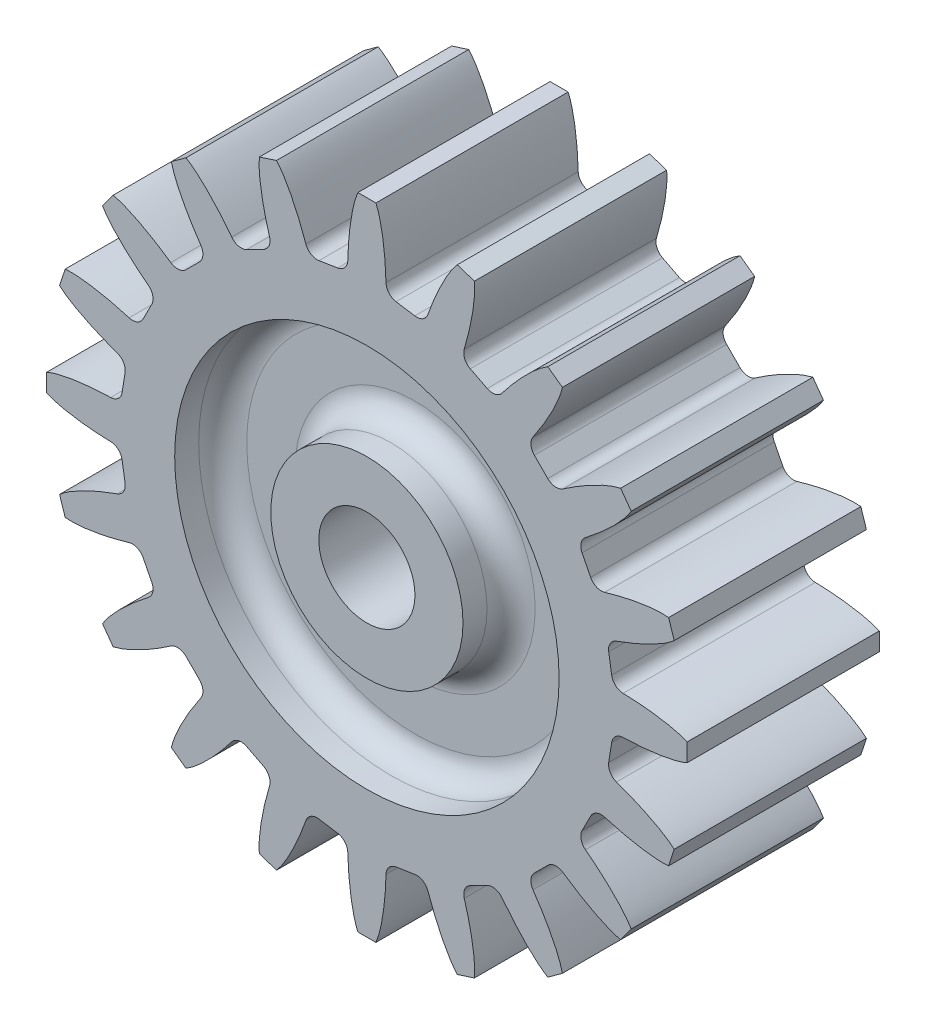
SolidWorks part; units mm, degrees
ref_plane "Front Plane" through (0, 0, 0) normal (0, 0, 1) x (1, 0, 0)
ref_plane "Top Plane" through (0, 0, 0) normal (0, 1, 0) x (1, 0, 0)
ref_plane "Right Plane" through (0, 0, 0) normal (1, 0, 0) x (0, 0, -1)
sketch "Sketch1" plane through (0, 0, 0) normal (0, 0, 1) x (1, 0, 0)
  line L0 (0, -63.5) -> (0, 63.5) construction
  line L1 (63.5, 0) -> (-63.5, 0) construction
  line L2 (-1.1938, 42.3123) -> (1.1938, 42.3123)
  line L3 (-14.2106, 39.8724) -> (-11.9398, 40.6103)
  line L4 (11.9398, 40.6103) -> (14.2106, 39.8724)
  line L5 (-3.8534, 32.3448) -> (-6.3303, 31.9525)
  line L6 (3.8534, 32.3448) -> (6.3303, 31.9525)
  line L7 (23.9047, 34.933) -> (25.8363, 33.5296)
  line L8 (33.5296, 25.8363) -> (34.933, 23.9047)
  line L9 (39.8724, 14.2106) -> (40.6103, 11.9398)
  line L10 (42.3123, 1.1938) -> (42.3123, -1.1938)
  line L11 (40.6103, -11.9398) -> (39.8724, -14.2106)
  line L12 (34.933, -23.9047) -> (33.5296, -25.8363)
  line L13 (13.6599, 29.571) -> (15.8943, 28.4325)
  line L14 (22.1293, 23.9025) -> (23.9025, 22.1293)
  line L15 (25.8363, -33.5296) -> (23.9047, -34.933)
  line L16 (14.2106, -39.8724) -> (11.9398, -40.6103)
  line L17 (1.1938, -42.3123) -> (-1.1938, -42.3123)
  line L18 (-14.2106, -39.8724) -> (-11.9398, -40.6103)
  line L19 (-25.8363, -33.5296) -> (-23.9047, -34.933)
  line L20 (-34.933, -23.9047) -> (-33.5296, -25.8363)
  line L21 (-39.8724, -14.2106) -> (-40.6103, -11.9398)
  line L22 (-42.3123, 1.1938) -> (-42.3123, -1.1938)
  line L23 (-39.8724, 14.2106) -> (-40.6103, 11.9398)
  line L24 (-34.933, 23.9047) -> (-33.5296, 25.8363)
  line L25 (-25.8363, 33.5296) -> (-23.9047, 34.933)
  line L26 (-15.8943, 28.4325) -> (-13.6599, 29.571)
  line L27 (-22.1293, 23.9025) -> (-23.9025, 22.1293)
  line L28 (-29.571, 13.6599) -> (-28.4325, 15.8943)
  line L29 (-31.9525, 6.3303) -> (-32.3448, 3.8534)
  line L30 (-32.3448, -3.8534) -> (-31.9525, -6.3303)
  line L31 (-29.571, -13.6599) -> (-28.4325, -15.8943)
  line L32 (-23.9025, -22.1293) -> (-22.1293, -23.9025)
  line L33 (-15.8943, -28.4325) -> (-13.6599, -29.571)
  line L34 (-6.3303, -31.9525) -> (-3.8534, -32.3448)
  line L35 (3.8534, -32.3448) -> (6.3303, -31.9525)
  line L36 (13.6599, -29.571) -> (15.8943, -28.4325)
  line L37 (22.1293, -23.9025) -> (23.9025, -22.1293)
  line L38 (29.571, -13.6599) -> (28.4325, -15.8943)
  line L39 (32.3448, -3.8534) -> (31.9525, -6.3303)
  line L40 (31.9525, 6.3303) -> (32.3448, 3.8534)
  line L41 (28.4325, 15.8943) -> (29.571, 13.6599)
  circle A0 centre (0, 0) radius 6.35
  circle A1 centre (0, 0) radius 12.7
  circle A2 centre (0, 0) radius 25.4
  circle A3 centre (0, 0) radius 42.3291 construction
  circle A4 centre (0, 0) radius 32.6517 construction
  circle A5 centre (0, 0) radius 38.0873 construction
  arc A6 (-3.8534, 32.3448) -> (-2.5255, 33.8596) centre (-4.0998, 33.9002) ccw
  arc A7 (-8.0613, 32.9828) -> (-6.3303, 31.9525) centre (-6.5766, 33.5079) ccw
  arc A8 (8.0613, 32.9828) -> (6.3303, 31.9525) centre (6.5766, 33.5079) cw
  arc A9 (2.5255, 33.8596) -> (3.8534, 32.3448) centre (4.0998, 33.9002) ccw
  arc A10 (12.8651, 31.422) -> (13.6599, 29.571) centre (14.3749, 30.9741) ccw
  arc A11 (17.859, 28.8775) -> (15.8943, 28.4325) centre (16.6092, 29.8356) cw
  arc A12 (25.9085, 21.9454) -> (23.9025, 22.1293) centre (25.0161, 23.2428) cw
  arc A13 (21.9454, 25.9085) -> (22.1293, 23.9025) centre (23.2428, 25.0161) ccw
  arc A14 (-13.6599, 29.571) -> (-12.8651, 31.422) centre (-14.3749, 30.9741) ccw
  arc A15 (-17.859, 28.8775) -> (-15.8943, 28.4325) centre (-16.6092, 29.8356) ccw
  arc A16 (-33.8596, 2.5255) -> (-32.3448, 3.8534) centre (-33.9002, 4.0998) ccw
  arc A17 (-31.9525, 6.3303) -> (-32.9828, 8.0613) centre (-33.5079, 6.5766) ccw
  arc A18 (-31.422, 12.8651) -> (-29.571, 13.6599) centre (-30.9741, 14.3749) ccw
  arc A19 (-28.4325, 15.8943) -> (-28.8775, 17.859) centre (-29.8356, 16.6092) ccw
  arc A20 (-25.9085, 21.9454) -> (-23.9025, 22.1293) centre (-25.0161, 23.2428) ccw
  arc A21 (-22.1293, 23.9025) -> (-21.9454, 25.9085) centre (-23.2428, 25.0161) ccw
  arc A22 (-32.9828, -8.0613) -> (-31.9525, -6.3303) centre (-33.5079, -6.5766) ccw
  arc A23 (-32.3448, -3.8534) -> (-33.8596, -2.5255) centre (-33.9002, -4.0998) ccw
  arc A24 (-28.8775, -17.859) -> (-28.4325, -15.8943) centre (-29.8356, -16.6092) ccw
  arc A25 (-31.422, -12.8651) -> (-29.571, -13.6599) centre (-30.9741, -14.3749) cw
  arc A26 (-21.9454, -25.9085) -> (-22.1293, -23.9025) centre (-23.2428, -25.0161) ccw
  arc A27 (-23.9025, -22.1293) -> (-25.9085, -21.9454) centre (-25.0161, -23.2428) ccw
  arc A28 (-12.8651, -31.422) -> (-13.6599, -29.571) centre (-14.3749, -30.9741) ccw
  arc A29 (-15.8943, -28.4325) -> (-17.859, -28.8775) centre (-16.6092, -29.8356) ccw
  arc A30 (-2.5255, -33.8596) -> (-3.8534, -32.3448) centre (-4.0998, -33.9002) ccw
  arc A31 (-6.3303, -31.9525) -> (-8.0613, -32.9828) centre (-6.5766, -33.5079) ccw
  arc A32 (8.0613, -32.9828) -> (6.3303, -31.9525) centre (6.5766, -33.5079) ccw
  arc A33 (2.5255, -33.8596) -> (3.8534, -32.3448) centre (4.0998, -33.9002) cw
  arc A34 (17.859, -28.8775) -> (15.8943, -28.4325) centre (16.6092, -29.8356) ccw
  arc A35 (13.6599, -29.571) -> (12.8651, -31.422) centre (14.3749, -30.9741) ccw
  arc A36 (21.9454, -25.9085) -> (22.1293, -23.9025) centre (23.2428, -25.0161) cw
  arc A37 (25.9085, -21.9454) -> (23.9025, -22.1293) centre (25.0161, -23.2428) ccw
  arc A38 (28.4325, -15.8943) -> (28.8775, -17.859) centre (29.8356, -16.6092) ccw
  arc A39 (31.422, -12.8651) -> (29.571, -13.6599) centre (30.9741, -14.3749) ccw
  arc A40 (32.9828, -8.0613) -> (31.9525, -6.3303) centre (33.5079, -6.5766) cw
  arc A41 (33.8596, -2.5255) -> (32.3448, -3.8534) centre (33.9002, -4.0998) ccw
  arc A42 (32.3448, 3.8534) -> (33.8596, 2.5255) centre (33.9002, 4.0998) ccw
  arc A43 (32.9828, 8.0613) -> (31.9525, 6.3303) centre (33.5079, 6.5766) ccw
  arc A44 (29.571, 13.6599) -> (31.422, 12.8651) centre (30.9741, 14.3749) ccw
  arc A45 (28.8775, 17.859) -> (28.4325, 15.8943) centre (29.8356, 16.6092) ccw
  ellipse E0 centre (0, 32.6517) end of major axis (0, 43.5952) minor radius 2.541 (2.5255, 33.8596) -> (1.1938, 42.3123) ccw
  ellipse E1 centre (19.1922, 26.4158) end of major axis (12.7598, 17.5623) minor radius 2.541 (21.9454, 25.9085) -> (25.8363, 33.5296) ccw
  ellipse E2 centre (26.4158, 19.1922) end of major axis (35.2692, 25.6246) minor radius 2.541 (28.8775, 17.859) -> (34.933, 23.9047) ccw
  ellipse E3 centre (31.0536, -10.0899) end of major axis (20.6457, -6.7082) minor radius 2.541 (31.422, -12.8651) -> (39.8724, -14.2106) ccw
  ellipse E4 centre (31.0536, 10.0899) end of major axis (20.6457, 6.7082) minor radius 2.541 (32.9828, 8.0613) -> (40.6103, 11.9398) ccw
  ellipse E5 centre (32.6517, 0) end of major axis (43.5952, 0) minor radius 2.541 (33.8596, -2.5255) -> (42.3123, -1.1938) ccw
  ellipse E6 centre (0, 32.6517) end of major axis (0, 43.5952) minor radius 2.541 (-1.1938, 42.3123) -> (-2.5255, 33.8596) ccw
  ellipse E7 centre (26.4158, -19.1922) end of major axis (35.2692, -25.6246) minor radius 2.541 (25.9085, -21.9454) -> (33.5296, -25.8363) ccw
  ellipse E8 centre (-10.0899, 31.0536) end of major axis (-6.7082, 20.6457) minor radius 2.541 (-14.2106, 39.8724) -> (-12.8651, 31.422) ccw
  ellipse E9 centre (10.0899, -31.0536) end of major axis (13.4717, -41.4615) minor radius 2.541 (8.0613, -32.9828) -> (11.9398, -40.6103) ccw
  ellipse E10 centre (10.0899, 31.0536) end of major axis (6.7082, 20.6457) minor radius 2.541 (11.9398, 40.6103) -> (8.0613, 32.9828) ccw
  ellipse E11 centre (-10.0899, -31.0536) end of major axis (-13.4717, -41.4615) minor radius 2.541 (-12.8651, -31.422) -> (-14.2106, -39.8724) ccw
  ellipse E12 centre (-19.1922, -26.4158) end of major axis (-25.6246, -35.2692) minor radius 2.541 (-21.9454, -25.9085) -> (-25.8363, -33.5296) ccw
  ellipse E13 centre (-26.4158, -19.1922) end of major axis (-17.5623, -12.7598) minor radius 2.541 (-28.8775, -17.859) -> (-34.933, -23.9047) ccw
  ellipse E14 centre (19.1922, -26.4158) end of major axis (12.7598, -17.5623) minor radius 2.541 (17.859, -28.8775) -> (23.9047, -34.933) ccw
  ellipse E15 centre (-32.6517, 0) end of major axis (-43.5952, 0) minor radius 2.541 (-33.8596, 2.5255) -> (-42.3123, 1.1938) ccw
  ellipse E16 centre (-31.0536, 10.0899) end of major axis (-41.4615, 13.4717) minor radius 2.541 (-31.422, 12.8651) -> (-39.8724, 14.2106) ccw
  ellipse E17 centre (-26.4158, 19.1922) end of major axis (-17.5623, 12.7598) minor radius 2.541 (-25.9085, 21.9454) -> (-33.5296, 25.8363) ccw
  ellipse E18 centre (-19.1922, 26.4158) end of major axis (-25.6246, 35.2692) minor radius 2.541 (-17.859, 28.8775) -> (-23.9047, 34.933) ccw
  ellipse E19 centre (-10.0899, 31.0536) end of major axis (-6.7082, 20.6457) minor radius 2.541 (-8.0613, 32.9828) -> (-11.9398, 40.6103) ccw
  ellipse E20 centre (10.0899, 31.0536) end of major axis (6.7082, 20.6457) minor radius 2.541 (12.8651, 31.422) -> (14.2106, 39.8724) ccw
  ellipse E21 centre (26.4158, -19.1922) end of major axis (35.2692, -25.6246) minor radius 2.541 (34.933, -23.9047) -> (28.8775, -17.859) ccw
  ellipse E22 centre (-31.0536, -10.0899) end of major axis (-20.6457, -6.7082) minor radius 2.541 (-32.9828, -8.0613) -> (-40.6103, -11.9398) ccw
  ellipse E23 centre (31.0536, -10.0899) end of major axis (20.6457, -6.7082) minor radius 2.541 (40.6103, -11.9398) -> (32.9828, -8.0613) ccw
  ellipse E24 centre (32.6517, 0) end of major axis (43.5952, 0) minor radius 2.541 (42.3123, 1.1938) -> (33.8596, 2.5255) ccw
  ellipse E25 centre (31.0536, 10.0899) end of major axis (20.6457, 6.7082) minor radius 2.541 (39.8724, 14.2106) -> (31.422, 12.8651) ccw
  ellipse E26 centre (0, -32.6517) end of major axis (0, -43.5952) minor radius 2.541 (-2.5255, -33.8596) -> (-1.1938, -42.3123) ccw
  ellipse E27 centre (26.4158, 19.1922) end of major axis (35.2692, 25.6246) minor radius 2.541 (33.5296, 25.8363) -> (25.9085, 21.9454) ccw
  ellipse E28 centre (19.1922, 26.4158) end of major axis (12.7598, 17.5623) minor radius 2.541 (23.9047, 34.933) -> (17.859, 28.8775) ccw
  ellipse E29 centre (-19.1922, 26.4158) end of major axis (-25.6246, 35.2692) minor radius 2.541 (-25.8363, 33.5296) -> (-21.9454, 25.9085) ccw
  ellipse E30 centre (-26.4158, 19.1922) end of major axis (-17.5623, 12.7598) minor radius 2.541 (-34.933, 23.9047) -> (-28.8775, 17.859) ccw
  ellipse E31 centre (-31.0536, 10.0899) end of major axis (-41.4615, 13.4717) minor radius 2.541 (-40.6103, 11.9398) -> (-32.9828, 8.0613) ccw
  ellipse E32 centre (-32.6517, 0) end of major axis (-43.5952, 0) minor radius 2.541 (-42.3123, -1.1938) -> (-33.8596, -2.5255) ccw
  ellipse E33 centre (-31.0536, -10.0899) end of major axis (-20.6457, -6.7082) minor radius 2.541 (-39.8724, -14.2106) -> (-31.422, -12.8651) ccw
  ellipse E34 centre (-26.4158, -19.1922) end of major axis (-17.5623, -12.7598) minor radius 2.541 (-33.5296, -25.8363) -> (-25.9085, -21.9454) ccw
  ellipse E35 centre (19.1922, -26.4158) end of major axis (12.7598, -17.5623) minor radius 2.541 (25.8363, -33.5296) -> (21.9454, -25.9085) ccw
  ellipse E36 centre (10.0899, -31.0536) end of major axis (13.4717, -41.4615) minor radius 2.541 (14.2106, -39.8724) -> (12.8651, -31.422) ccw
  ellipse E37 centre (0, -32.6517) end of major axis (0, -43.5952) minor radius 2.541 (1.1938, -42.3123) -> (2.5255, -33.8596) ccw
  ellipse E38 centre (-10.0899, -31.0536) end of major axis (-13.4717, -41.4615) minor radius 2.541 (-11.9398, -40.6103) -> (-8.0613, -32.9828) ccw
  ellipse E39 centre (-19.1922, -26.4158) end of major axis (-25.6246, -35.2692) minor radius 2.541 (-23.9047, -34.933) -> (-17.859, -28.8775) ccw
  point P11 (0, 0)
  point P13 (0, 0)
  point P15 (-1.1938, 42.3123)
  point P21 (1.1938, 42.3123)
  point P22 (2.2139, 38.0229)
  point P23 (-2.2139, 38.0229)
  point P28 (11.9398, 40.6103)
  point P34 (14.2106, 39.8724)
  point P35 (13.8553, 35.4778)
  point P36 (9.6442, 36.8461)
  point P38 (23.9047, 34.933)
  point P44 (25.8363, 33.5296)
  point P45 (24.1404, 29.4599)
  point P46 (20.5582, 32.0625)
  point P48 (33.5296, 25.8363)
  point P54 (34.933, 23.9047)
  point P55 (32.0625, 20.5582)
  point P56 (29.4599, 24.1404)
  point P58 (39.8724, 14.2106)
  point P64 (40.6103, 11.9398)
  point P65 (36.8461, 9.6442)
  point P66 (35.4778, 13.8553)
  point P68 (42.3123, 1.1938)
  point P74 (42.3123, -1.1938)
  point P75 (38.0229, -2.2139)
  point P76 (38.0229, 2.2139)
  point P78 (40.6103, -11.9398)
  point P84 (39.8724, -14.2106)
  point P85 (35.4778, -13.8553)
  point P86 (36.8461, -9.6442)
  point P88 (34.933, -23.9047)
  point P94 (33.5296, -25.8363)
  point P95 (29.4599, -24.1404)
  point P96 (32.0625, -20.5582)
  point P98 (25.8363, -33.5296)
  point P104 (23.9047, -34.933)
  point P105 (20.5582, -32.0625)
  point P106 (24.1404, -29.4599)
  point P108 (14.2106, -39.8724)
  point P114 (11.9398, -40.6103)
  point P115 (9.6442, -36.8461)
  point P116 (13.8553, -35.4778)
  point P118 (1.1938, -42.3123)
  point P124 (-1.1938, -42.3123)
  point P125 (-2.2139, -38.0229)
  point P126 (2.2139, -38.0229)
  point P128 (-11.9398, -40.6103)
  point P134 (-14.2106, -39.8724)
  point P135 (-13.8553, -35.4778)
  point P136 (-9.6442, -36.8461)
  point P138 (-23.9047, -34.933)
  point P144 (-25.8363, -33.5296)
  point P145 (-24.1404, -29.4599)
  point P146 (-20.5582, -32.0625)
  point P148 (-33.5296, -25.8363)
  point P154 (-34.933, -23.9047)
  point P155 (-32.0625, -20.5582)
  point P156 (-29.4599, -24.1404)
  point P158 (-39.8724, -14.2106)
  point P164 (-40.6103, -11.9398)
  point P165 (-36.8461, -9.6442)
  point P166 (-35.4778, -13.8553)
  point P168 (-42.3123, -1.1938)
  point P174 (-42.3123, 1.1938)
  point P175 (-38.0229, 2.2139)
  point P176 (-38.0229, -2.2139)
  point P178 (-40.6103, 11.9398)
  point P184 (-39.8724, 14.2106)
  point P185 (-35.4778, 13.8553)
  point P186 (-36.8461, 9.6442)
  point P188 (-34.933, 23.9047)
  point P194 (-33.5296, 25.8363)
  point P195 (-29.4599, 24.1404)
  point P196 (-32.0625, 20.5582)
  point P198 (-25.8363, 33.5296)
  point P204 (-23.9047, 34.933)
  point P205 (-20.5582, 32.0625)
  point P206 (-24.1404, 29.4599)
  point P208 (-14.2106, 39.8724)
  point P214 (-11.9398, 40.6103)
  point P215 (-9.6442, 36.8461)
  point P216 (-13.8553, 35.4778)
  dimension "D1" = 12.7
  dimension "D2" = 25.4
  dimension "D3" = 50.8
  dimension "D4" = 84.6582
  dimension "D5" = 65.3034
  dimension "D6" = 76.1746
  dimension "D11" = 1.5748
  dimension "D12" = 1.5748
  dimension "D17" = 1.5748
  dimension "D18" = 1.5748
  dimension "D23" = 1.5748
  dimension "D26" = 1.5748
  dimension "D29" = 1.5748
  dimension "D32" = 1.5748
  dimension "D35" = 1.5748
  dimension "D38" = 1.5748
  dimension "D41" = 1.5748
  dimension "D44" = 1.5748
  dimension "D47" = 1.5748
  dimension "D50" = 1.5748
  dimension "D53" = 1.5748
  dimension "D56" = 1.5748
  dimension "D59" = 1.5748
  dimension "D62" = 1.5748
  dimension "D65" = 1.5748
  dimension "D68" = 1.5748
  dimension "D7" = 127
  dimension "D8" = 127
  dimension "D9" = 2.3876
  dimension "D10" = 4.4278
  dimension "D13" = 2.5077
  dimension "D14" = 5.6048
  dimension "D15" = 2.5077
  dimension "D16" = 5.6048
  dimension "D19" = 2.5077
  dimension "D20" = 5.6048
  dimension "D21" = 2.5077
  dimension "D22" = 5.6048
  dimension "D24" = 2.5077
  dimension "D25" = 5.6048
  dimension "D27" = 2.4768
  dimension "D28" = 5.5358
  dimension "D30" = 2.5077
  dimension "D31" = 5.6048
  dimension "D33" = 2.5077
  dimension "D34" = 5.6048
  dimension "D36" = 2.4768
  dimension "D37" = 5.5358
  dimension "D39" = 5.6048
  dimension "D40" = 2.5077
  dimension "D42" = 5.6048
  dimension "D43" = 2.5077
  dimension "D45" = 5.6048
  dimension "D46" = 2.5077
  dimension "D48" = 5.6048
  dimension "D49" = 2.5077
  dimension "D51" = 2.5077
  dimension "D52" = 5.6048
  dimension "D54" = 2.5077
  dimension "D55" = 5.6048
  dimension "D57" = 2.5077
  dimension "D58" = 5.6048
  dimension "D60" = 2.5077
  dimension "D61" = 5.6048
  dimension "D63" = 2.5077
  dimension "D64" = 5.6048
  dimension "D66" = 2.4768
  dimension "D67" = 5.6048
  dimension "D69" = 2.5077
  dimension "D70" = 5.6048
extrude "Boss-Extrude1" add sketch "Sketch1" along normal blind 25.4 contours L19 E39 A29 L33 A28 E11 L18 E38 A31 L34 A30 E26 L17 E37 A33 L35 A32 E9 L16 E36 A35 L36 A34 E14 L15 E35 A36 L37 A37 E7 L12 E21 A38 L38 A39 E3 L11 E23 A40 L39 A41 E5 L10 E24 A42 L40 A43 E4 L9 E25 A44 | A2 region at (0, 41.1155, 0)
extrude "Cut-Extrude5" cut sketch "Sketch1<3>" along normal through all contours A0 region at (0, 0, 0)
sketch "Sketch1<3>" plane through (0, 0, 0) normal (0, 0, 1) x (1, 0, 0) same geometry as "Sketch1"
extrude "Cut-Extrude6" cut sketch "Sketch1<4>" along normal blind 6.35 contours A2 A1 region at (-24.6816, 0, 0)
sketch "Sketch1<4>" plane through (0, 0, 0) normal (0, 0, 1) x (1, 0, 0) same geometry as "Sketch1"
fillet "Fillet1" radius 3.175 2 edges at (12.7, 0, 6.35) (25.4, 0, 6.35)
ref_plane "Plane1" through (0, 0, 12.7) normal (0, 0, -1) x (-1, 0, 0)
mirror "Mirror2" about plane through (0, 0, 12.7) normal (0, 0, -1) of "Fillet1", "Cut-Extrude6"
